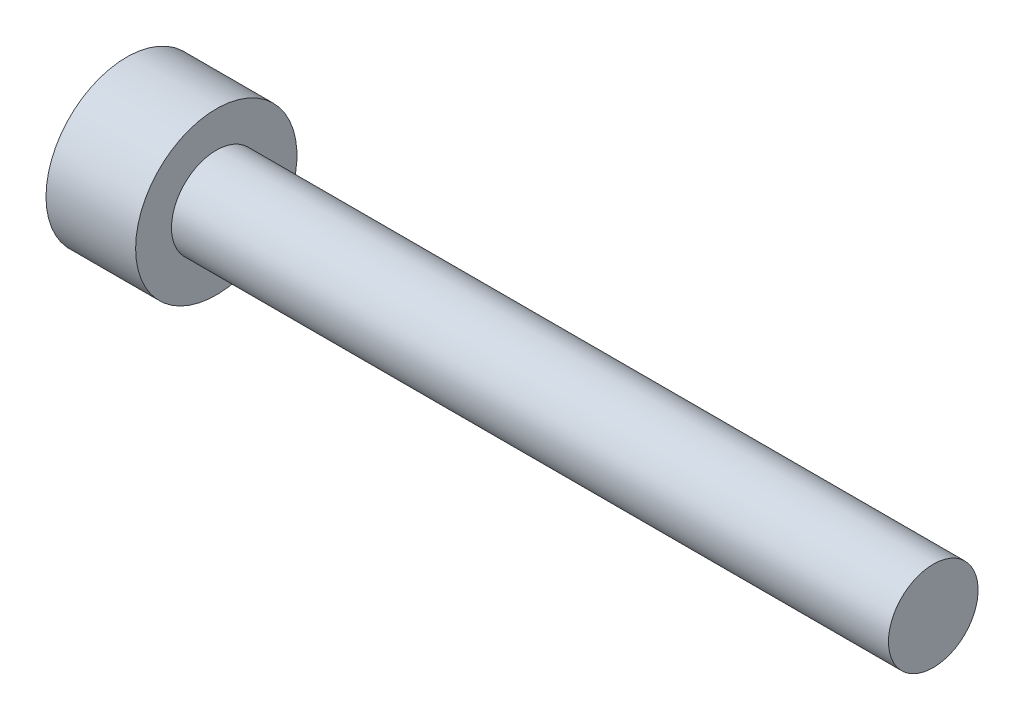
SolidWorks part; units mm, degrees
ref_plane "Front Plane" through (0, 0, 0) normal (0, 0, 1) x (1, 0, 0)
ref_plane "Top Plane" through (0, 0, 0) normal (0, 1, 0) x (1, 0, 0)
ref_plane "Right Plane" through (0, 0, 0) normal (1, 0, 0) x (0, 0, -1)
sketch "Screw Sketch" plane through (0, 0, 0) normal (0, 0, 1) x (1, 0, 0)
  line L0 (-400, 0) -> (400, 0) construction
  line L1 (-2.5, 0) -> (-2.5, 2.25)
  line L2 (-2.5, 2.25) -> (0, 2.25)
  line L3 (0, 2.25) -> (0, 1.25)
  line L4 (0, 1.25) -> (20, 1.25)
  line L5 (20, 1.25) -> (20, 0)
  line L6 (20, 0) -> (-2.5, 0)
revolve "Screw" add sketch "Screw Sketch" angle 360 about L0
ref_axis "Engine Axis" through (21.125, 0, 0) along (-1, 0, 0)
ref_plane "Head Top" through (-2.5, 0, 0) normal (1, 0, 0) x (0, 0, -1)
sketch "Socket Sketch" plane through (-2.5, 0, 0) normal (1, 0, 0) x (0, 0, -1)
  line L0 (1.1547, 0) -> (0.5774, 1)
  line L1 (0.5774, 1) -> (-0.5774, 1)
  line L2 (-0.5774, 1) -> (-1.1547, 0)
  line L3 (-1.1547, 0) -> (-0.5774, -1)
  line L4 (-0.5774, -1) -> (0.5774, -1)
  line L5 (0.5774, -1) -> (1.1547, 0)
extrude "Socket" cut sketch "Socket Sketch" along normal blind 1.25
